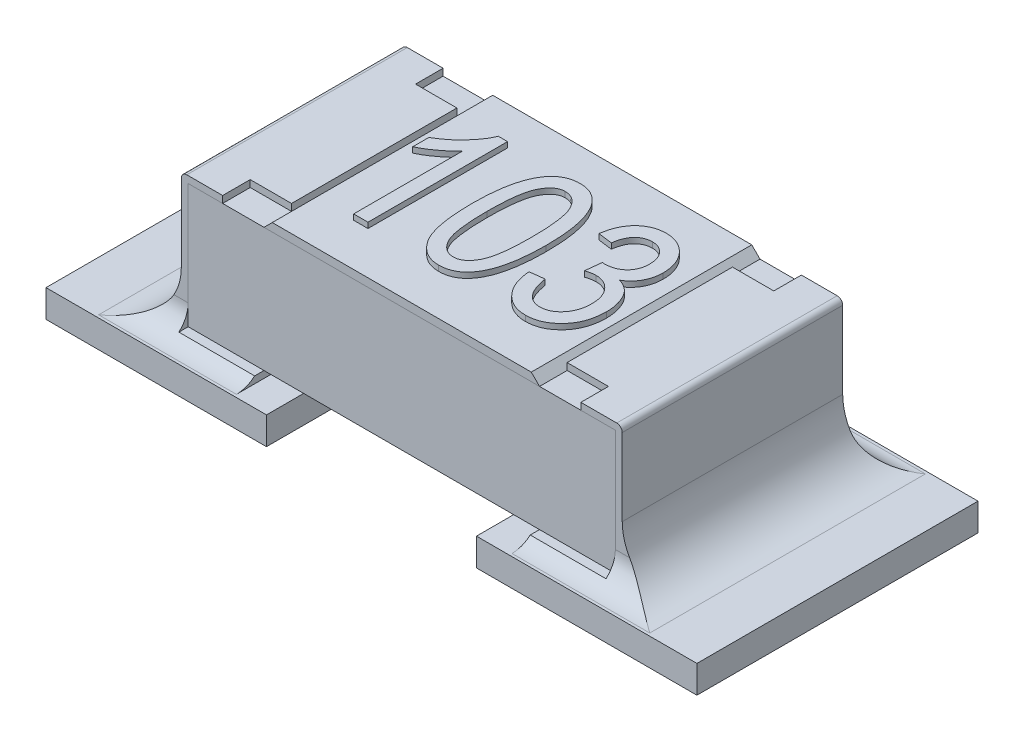
SolidWorks part; units mm, degrees
material "Ceramic Porcelain"
ref_plane "Front Plane" through (0, 0, 0) normal (0, 0, 1) x (1, 0, 0)
ref_plane "Top Plane" through (0, 0, 0) normal (0, 1, 0) x (1, 0, 0)
ref_plane "Right Plane" through (0, 0, 0) normal (1, 0, 0) x (0, 0, -1)
sketch "Sketch1" plane through (0, 0, 0) normal (1, 0, 0) x (0, 0, -1)
  line L0 (0, 55) -> (0, -55) construction
  line L1 (-0.4, 0.575) -> (0.4, 0.575)
  line L2 (-0.4, 0.575) -> (-0.4, 0.125)
  line L3 (-0.4, 0.125) -> (0.4, 0.125)
  line L4 (0.4, 0.575) -> (0.4, 0.125)
  line L5 (55, 0) -> (-55, 0) construction
  dimension "D1" = 0.8
  dimension "D2" = 0.4
  dimension "D3" = 0.45
  dimension "D4" = 0.125
extrude "Boss-Extrude1" add sketch "Sketch1" along normal mid plane 1.55
sketch "Sketch2" plane through (0, 0, 0) normal (0, 0, 1) x (1, 0, 0)
  line L0 (-0.5, 0.6) -> (-0.78, 0.6)
  line L1 (-0.8, 0.58) -> (-0.8, 0.1)
  line L2 (-0.8, 0.1) -> (-0.5, 0.1)
  line L3 (-0.5, 0.1) -> (-0.5, 0.125)
  line L4 (0.775, 0.125) -> (-0.775, 0.125) construction
  line L5 (-0.5, 0.125) -> (-0.775, 0.125)
  line L6 (-0.775, 0.125) -> (-0.775, 0.575)
  line L7 (-0.775, 0.575) -> (-0.5, 0.575)
  line L8 (0.775, 0.575) -> (-0.775, 0.575) construction
  line L9 (-0.5, 0.575) -> (-0.5, 0.6)
  line L11 (0.5, 0.575) -> (0.5, 0.6)
  line L12 (0.5, 0.6) -> (0.78, 0.6)
  line L13 (0.8, 0.58) -> (0.8, 0.1)
  line L14 (0.8, 0.1) -> (0.5, 0.1)
  line L15 (0.5, 0.1) -> (0.5, 0.125)
  line L16 (0.5, 0.125) -> (0.775, 0.125)
  line L17 (0.775, 0.125) -> (0.775, 0.575)
  line L18 (0.775, 0.575) -> (0.5, 0.575)
  arc A0 (0.78, 0.6) -> (0.8, 0.58) centre (0.78, 0.58) cw
  arc A1 (-0.78, 0.6) -> (-0.8, 0.58) centre (-0.78, 0.58) ccw
  point P28 (-0.8, 0.6)
  dimension "D6" = 0.02
  dimension "D1" = 0.025
  dimension "D2" = 0.025
  dimension "D3" = 0.025
  dimension "D4" = 0.3
  dimension "D5" = 0.3
extrude "Boss-Extrude2" add sketch "Sketch2" along normal mid plane 0.8 separate body
sketch "Sketch3" plane through (0, 0.6, 0) normal (0, 1, 0) x (1, 0, 0)
  line L0 (0.5, -0.4) -> (0.5, 0.4) construction
  line L1 (-0.5, 0.4) -> (-0.65, 0.4)
  line L2 (-0.5, 0.4) -> (-0.5, 0.3)
  line L3 (-0.5, 0.3) -> (-0.65, 0.3)
  line L4 (-0.65, 0.4) -> (-0.65, 0.3)
  line L5 (-0.5, -0.4) -> (-0.65, -0.4)
  line L6 (-0.5, -0.4) -> (-0.5, -0.3)
  line L7 (-0.5, -0.3) -> (-0.65, -0.3)
  line L8 (-0.65, -0.4) -> (-0.65, -0.3)
  line L9 (0.5, -0.4) -> (0.65, -0.4)
  line L10 (0.5, -0.4) -> (0.5, -0.3)
  line L11 (0.5, -0.3) -> (0.65, -0.3)
  line L12 (0.65, -0.4) -> (0.65, -0.3)
  line L13 (0.775, -0.4) -> (-0.775, -0.4) construction
  line L15 (0.5, 0.4) -> (0.65, 0.4)
  line L16 (0.5, 0.4) -> (0.5, 0.3)
  line L17 (0.5, 0.3) -> (0.65, 0.3)
  line L18 (0.65, 0.4) -> (0.65, 0.3)
  dimension "D1" = 0.15
  dimension "D2" = 0.1
extrude "Cut-Extrude1" cut sketch "Sketch3" against normal blind 0.025
sketch "Sketch4" plane through (0, 0, 0) normal (0, 0, 1) x (1, 0, 0)
  line L0 (-0.5, 0.575) -> (0.5, 0.575)
  line L1 (0.5, 0.575) -> (0.47, 0.605)
  line L2 (0.47, 0.605) -> (-0.47, 0.605)
  line L3 (-0.47, 0.605) -> (-0.5, 0.575)
  dimension "D1" = 45
  dimension "D2" = 45
  dimension "D3" = 0.03
extrude "Boss-Extrude3" add sketch "Sketch4" along normal mid plane 0.8 separate body
sketch "Sketch7" plane through (0, 0, 0) normal (0, 1, 0) x (1, 0, 0)
  line L0 (0, -0.2833) -> (0, 0.2833) construction
  line L1 (-0.381, -0.51) -> (-1.181, -0.51)
  line L2 (-0.381, -0.51) -> (-0.381, 0.51)
  line L3 (-0.381, 0.51) -> (-1.181, 0.51)
  line L4 (-1.181, -0.51) -> (-1.181, 0.51)
  line L5 (0.381, -0.51) -> (1.181, -0.51)
  line L6 (0.381, -0.51) -> (0.381, 0.51)
  line L7 (0.381, 0.51) -> (1.181, 0.51)
  line L8 (1.181, -0.51) -> (1.181, 0.51)
  line L9 (-0.2833, 0) -> (0.2833, 0) construction
  dimension "D1" = 0.8
  dimension "D2" = 0.381
  dimension "D3" = 0.381
  dimension "D4" = 1.02
  dimension "D5" = 0.51
extrude "Boss-Extrude5" add sketch "Sketch7" along normal blind 0.1
fillet "Fillet3" radius 0.2 1 edges at (-0.8, 0.1, 0)
fillet "Fillet4" radius 0.2 1 edges at (0.8, 0.1, 0)
fillet "Fillet5" radius 0.1 2 edges at (0.75, 0.1, -0.4) (0.75, 0.1, 0.4)
fillet "Fillet6" radius 0.1 2 edges at (-0.75, 0.1, 0.4) (-0.75, 0.1, -0.4)
sketch "Esquisse2" plane through (0, 0.605, 0) normal (0, 1, 0) x (1, 0, 0)
  text T0 "103\r\n" font "Arial Narrow" height 0.5
extrude "Boss.-Extru.1" add sketch "Esquisse2" along normal blind 0.02
